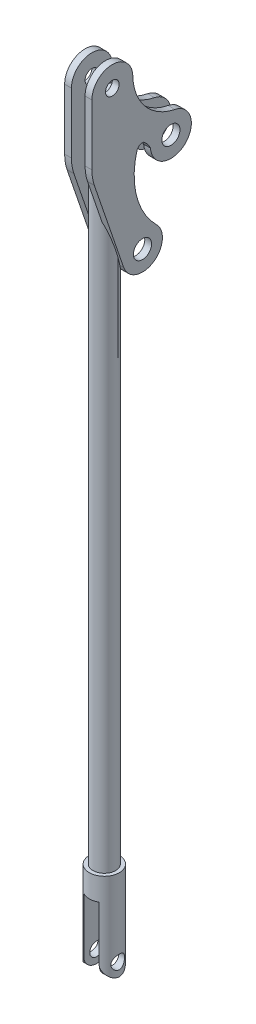
SolidWorks part; units mm, degrees
material "7075-O (SS)"
ref_plane "前视基准面" through (0, 0, 0) normal (0, 0, 1) x (1, 0, 0)
ref_plane "上视基准面" through (0, 0, 0) normal (0, 1, 0) x (1, 0, 0)
ref_plane "右视基准面" through (0, 0, 0) normal (1, 0, 0) x (0, 0, -1)
sketch "草图1" plane through (0, 0, 0) normal (0, 1, 0) x (1, 0, 0)
  circle A0 centre (0, 0) radius 2.5
  circle A1 centre (0, 0) radius 1
  dimension "D1" = 2
  dimension "D2" = 5
extrude "凸台-拉伸1" add sketch "草图1" along normal blind 160
sketch "草图2" plane through (0, 0, 0) normal (0, -1, 0) x (1, 0, 0)
  circle A0 centre (0, 0) radius 3.3
  dimension "D1" = 6.6
extrude "凸台-拉伸2" add sketch "草图2" along normal blind 10 and the other way blind 10
sketch "草图3" plane through (0, -10, 0) normal (0, -1, 0) x (1, 0, 0)
  line L0 (0, 0) -> (1.7, 0) construction
  line L1 (1.7, 0) -> (1.7, 2.8284) construction
  line L2 (1.7, 2.8284) -> (1.7, -2.8284)
  line L3 (0, 0) -> (0, -3.3) construction
  line L4 (-1.7, 2.8284) -> (-1.7, -2.8284)
  circle A0 centre (0, 0) radius 3.3 construction
  arc A1 (1.7, 2.8284) -> (-1.7, 2.8284) centre (0, 0) ccw
  arc A2 (-1.7, -2.8284) -> (1.7, -2.8284) centre (0, 0) ccw
  dimension "D1" = 3.4
extrude "切除-拉伸1" cut sketch "草图3" against normal blind 15
sketch "草图4" plane through (1.7, 0, 0) normal (-1, 0, 0) x (0, 0, 1)
  line L0 (0, -10) -> (0, -7) construction
  line L1 (-2.8284, -10) -> (2.8284, -10) construction
  line L2 (2.8284, -7) -> (2.8284, -10)
  line L3 (2.8284, -10) -> (-2.8284, -10)
  line L4 (-2.8284, -10) -> (-2.8284, -7)
  circle A0 centre (0, -7) radius 1.5
  arc A2 (-2.8284, -7) -> (2.8284, -7) centre (0, -7) ccw
extrude "切除-拉伸2" cut sketch "草图4" against normal through all and the other way through all
ref_plane "基准面1" through (1.5, 0, 0) normal (1, 0, 0) x (0, 0, -1)
sketch "草图5" plane through (1.5, 0, 0) normal (1, 0, 0) x (0, 0, -1)
  line L0 (0, 160) -> (-1.235, 160) construction
  line L1 (2.5, 160) -> (-2.5, 160) construction
  line L2 (-1.235, 160) -> (11.6541, 144.6393) construction
  line L3 (-1.235, 160) -> (-1.235, 126.0005) construction
  line L4 (-1.235, 126.0005) -> (5.401, 126.0005) construction
  line L5 (-5.7368, 160) -> (-5.7368, 146.6725)
  line L6 (-5.198, 143.4343) -> (1.2546, 124.5813)
  line L7 (5.2096, 152.3197) -> (5.9584, 152.948) construction
  line L8 (5.401, 126.0005) -> (5.401, 145.001) construction
  line L9 (5.401, 145.001) -> (11.6541, 144.6393) construction
  line L10 (9.7622, 156.1398) -> (14.7845, 160.354) construction
  line L11 (6.5131, 136.5881) -> (20.1164, 140.8951) construction
  circle A0 centre (-1.235, 160) radius 1.5
  arc A1 (3.2657, 160.0994) -> (-5.7368, 160) centre (-1.235, 160) ccw
  arc A2 (7.1605, 144.3695) -> (12.5336, 149.0543) centre (11.6541, 144.6393) ccw
  circle A3 centre (11.6541, 144.6393) radius 2
  arc A4 (1.2546, 124.5813) -> (8.5217, 129.0775) centre (5.401, 126.0005) ccw
  circle A5 centre (5.401, 126.0005) radius 2
  arc A7 (-5.7368, 146.6725) -> (-5.198, 143.4343) centre (4.2632, 146.6725) ccw
  arc A8 (3.2657, 160.0994) -> (12.5336, 149.0543) centre (14.7845, 160.354) ccw
  arc A9 (5.7159, 146.2399) -> (4.1727, 145.3551) centre (5.401, 145.001) ccw
  arc A11 (4.1727, 145.3551) -> (8.5217, 129.0775) centre (20.1164, 140.8951) ccw
  arc A15 (7.1605, 144.3695) -> (5.7159, 146.2399) centre (2.0421, 141.9096) ccw
  dimension "D1" = 40
  dimension "D2" = 10
extrude "凸台-拉伸4" add sketch "草图5" along normal blind 1.5
mirror "镜向1" about plane through (0, 0, 0) normal (1, 0, 0) of "凸台-拉伸4"
sketch "草图6" plane through (3, 0, 0) normal (1, 0, 0) x (0, 0, -1)
  circle A0 centre (-1.235, 160) radius 1.5
extrude "切除-拉伸3" cut sketch "草图6" against normal through all
sketch "草图7" plane through (0, 0, 0) normal (1, 0, 0) x (0, 0, -1)
  circle A0 centre (-1.235, 160) radius 4.5018
extrude "切除-拉伸4" cut sketch "草图7" against normal blind 1.5 and the other way blind 1.5
